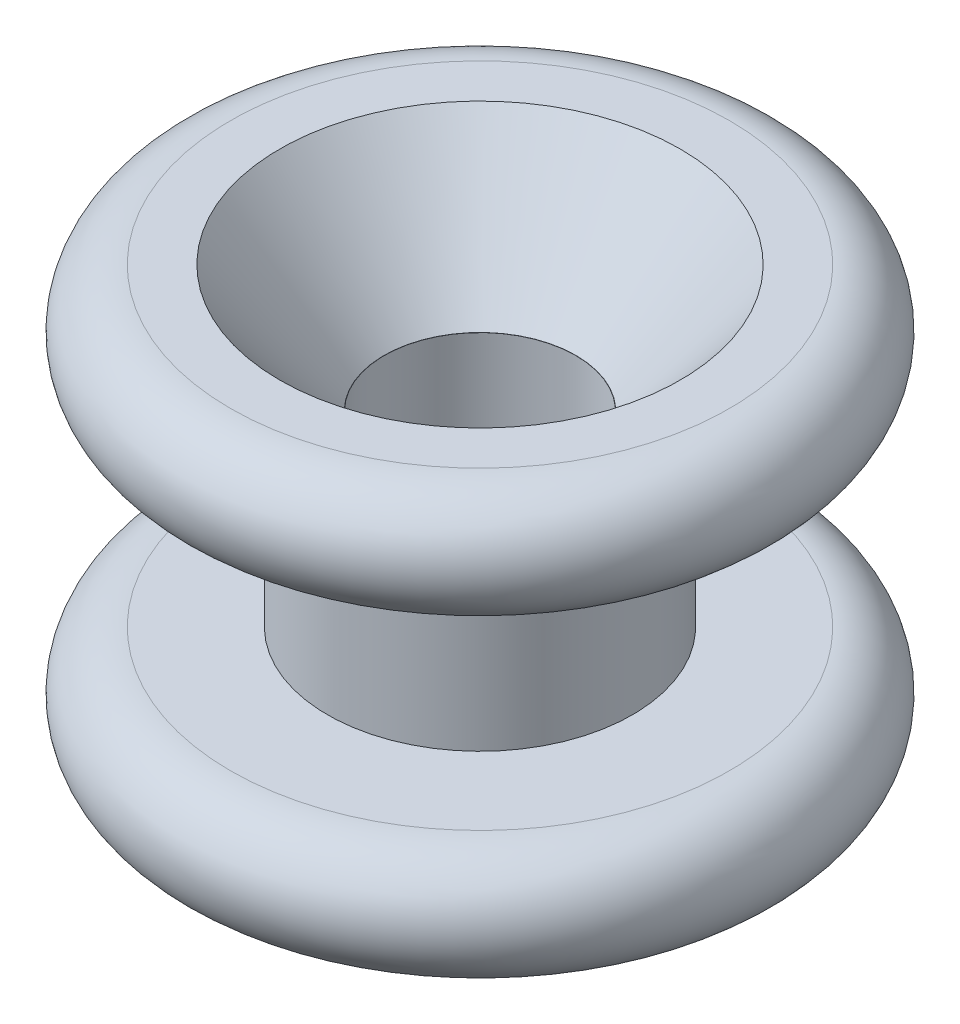
SolidWorks part; units mm, degrees
material "Delrin 2700 NC010, Low Viscosity Acetal Copolymer (SS)"
ref_plane "Front Plane" through (0, 0, 0) normal (0, 0, 1) x (1, 0, 0)
ref_plane "Top Plane" through (0, 0, 0) normal (0, 1, 0) x (1, 0, 0)
ref_plane "Right Plane" through (0, 0, 0) normal (1, 0, 0) x (0, 0, -1)
sketch "Sketch2" plane through (0, 0, 0) normal (0, 0, 1) x (1, 0, 0)
  line L0 (2.4968, -5.588) -> (2.4968, 5.588)
  line L1 (2.4968, 5.588) -> (6.5024, 5.588)
  line L2 (6.5024, 2.5908) -> (3.9751, 2.5908)
  line L3 (3.9751, 2.5908) -> (3.9751, -2.5908)
  line L4 (8.001, 4.0894) -> (8.001, 5.588) construction
  line L5 (0, 0) -> (3.9751, 0) construction
  line L6 (2.4968, -5.588) -> (6.5024, -5.588)
  line L7 (6.5024, -2.5908) -> (3.9751, -2.5908)
  line L8 (0, 0) -> (0, 5.588) construction
  arc A0 (6.5024, 5.588) -> (6.5024, 2.5908) centre (6.5024, 4.0894) cw
  arc A1 (6.5024, -5.588) -> (6.5024, -2.5908) centre (6.5024, -4.0894) ccw
  point P0 (0, 0)
  point P17 (2.4968, 0)
  dimension "D1" = 5.588
  dimension "D2" = 2.4968
  dimension "D3" = 3.9751
  dimension "D4" = 2.9972
  dimension "D5" = 8.001
revolve "Revolve1" add sketch "Sketch2" angle 360 about L8
sketch "Sketch3" plane through (0, 0, 0) normal (0, 0, 1) x (1, 0, 0)
  line L0 (0, 5.588) -> (5.2197, 5.588)
  line L1 (2.4968, 5.588) -> (-2.4968, 5.588) construction
  line L2 (6.5024, 5.588) -> (-6.5024, 5.588) construction
  line L3 (5.2197, 5.588) -> (2.5019, 2.286)
  line L4 (2.5019, 2.286) -> (0, 2.286)
  line L5 (0, 2.286) -> (0, 5.588)
  dimension "D1" = 5.2197
  dimension "D2" = 2.5019
  dimension "D3" = 3.302
revolve "Cut-Revolve1" cut sketch "Sketch3" angle 360 about L5
